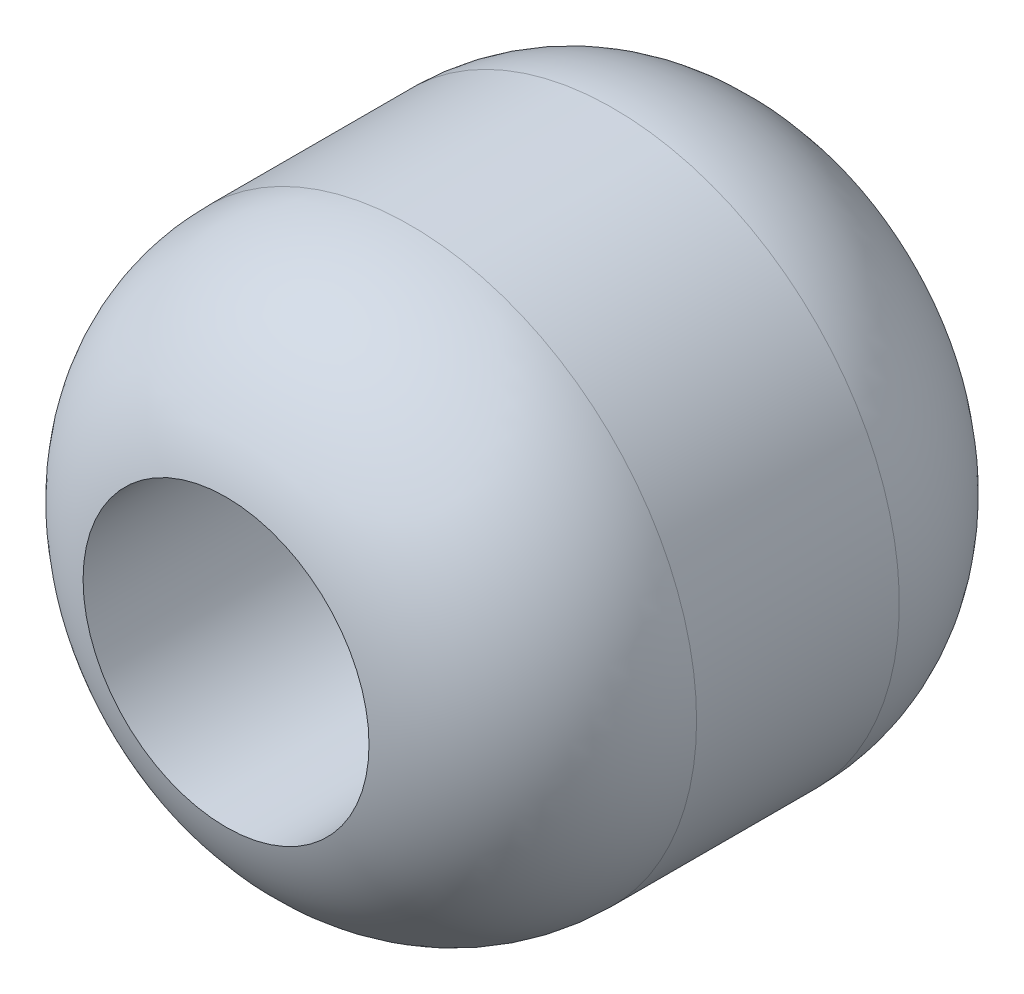
SolidWorks part; units mm, degrees
ref_plane "Front Plane" through (0, 0, 0) normal (0, 0, 1) x (1, 0, 0)
ref_plane "Top Plane" through (0, 0, 0) normal (0, 1, 0) x (1, 0, 0)
ref_plane "Right Plane" through (0, 0, 0) normal (1, 0, 0) x (0, 0, -1)
sketch "Sketch1" plane through (0, 0, 0) normal (0, 0, 1) x (1, 0, 0)
  circle A0 centre (0, 0) radius 7.5
  circle A1 centre (0, 0) radius 3.75
  dimension "D1" = 15
  dimension "D2" = 7.5
extrude "Boss-Extrude1" add sketch "Sketch1" along normal blind 15
fillet "Fillet1" radius 5 1 edges at (7.5, 0, 15)
fillet "Fillet2" radius 5 1 edges at (7.5, 0, 0)
